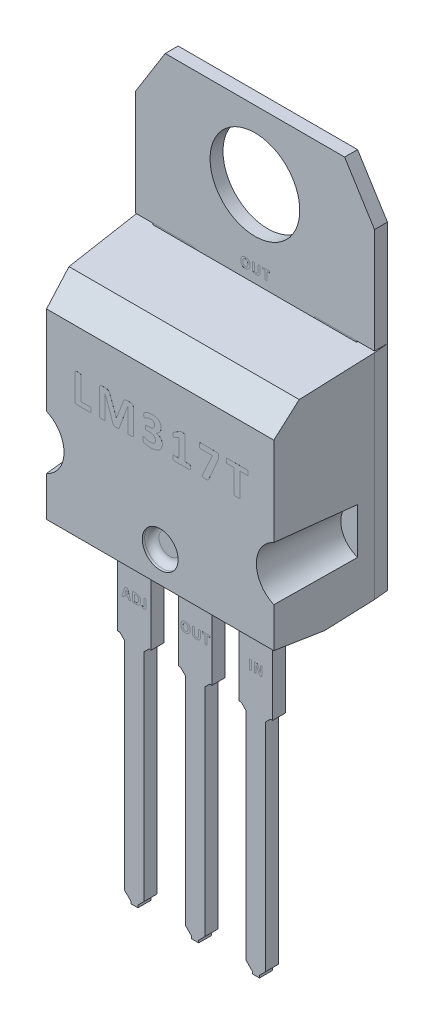
SolidWorks part; units mm, degrees
material "6061-T6 (SS)"
ref_plane "Front Plane" through (0, 0, 0) normal (0, 0, 1) x (1, 0, 0)
ref_plane "Top Plane" through (0, 0, 0) normal (0, 1, 0) x (1, 0, 0)
ref_plane "Right Plane" through (0, 0, 0) normal (1, 0, 0) x (0, 0, -1)
sketch "Sketch1" plane through (0, 0, 0) normal (1, 0, 0) x (0, 0, -1)
  line L0 (-0.27, 0) -> (0.27, 0) construction
  line L1 (0.27, 0) -> (2.77, 0) construction
  line L2 (2.77, 0) -> (2.77, 0.2628) construction
  line L3 (2.77, 0.2628) -> (0.27, 0)
  line L4 (2.77, 0.2628) -> (2.77, 9.2)
  line L5 (-0.27, 0) -> (-1.73, 0) construction
  line L6 (-1.73, 0) -> (-1.73, 0.2102) construction
  line L7 (0.27, 0) -> (-1.73, 0.2102)
  line L8 (-1.73, 0.2102) -> (-1.73, 7.8321)
  line L9 (2.77, 9.2) -> (-0.73, 8.8321)
  line L10 (-0.73, 8.8321) -> (-1.73, 8.727) construction
  line L11 (-1.73, 8.727) -> (-1.73, 7.8321) construction
  line L12 (-1.73, 7.8321) -> (-0.73, 8.8321)
  line L13 (2.77, 9.2) -> (-1.73, 9.2) construction
  line L14 (-1.73, 9.2) -> (-1.73, 8.727) construction
  line L15 (-0.73, 8.8321) -> (-0.73, 9.2) construction
  dimension "D1" = 0.54
  dimension "D2" = 2.5
  dimension "D3" = 9.2
  dimension "D4" = 6
  dimension "D5" = 4.5
  dimension "D6" = 6
  dimension "D7" = 45
  dimension "D8" = 3.5
extrude "Boss-Extrude1" add sketch "Sketch1" along normal mid plane 10
sketch "Sketch2" plane through (0, 0, 0) normal (0, 1, 0) x (1, 0, 0)
  line L0 (0, 0) -> (0, 2.77) construction
  line L1 (5, 2.77) -> (-5, 2.77) construction
  line L2 (-5, 2.77) -> (5, 2.77) construction
  line L3 (5, 2.77) -> (5, 2.23) construction
  line L4 (-5, 2.77) -> (-5, 2.23) construction
  line L5 (0, 0) -> (0, -1.73) construction
  line L6 (5, -1.73) -> (-5, -1.73) construction
  line L7 (-4.75, -1.73) -> (4.75, -1.73) construction
  line L8 (-4.75, -1.73) -> (-5, 2.23)
  line L9 (4.75, -1.73) -> (5, 2.23)
  line L10 (-4.75, -1.73) -> (-5, -1.73)
  line L11 (-5, -1.73) -> (-5, 2.23)
  line L12 (4.75, -1.73) -> (5, -1.73)
  line L13 (5, -1.73) -> (5, 2.23)
  dimension "D1" = 0.54
  dimension "D2" = 9.5
extrude "Cut-Extrude1" cut sketch "Sketch2" along normal through all
sketch "Sketch3" plane through (0, 0, -2.77) normal (0, 0, -1) x (-1, 0, 0)
  line L0 (0, 0) -> (0, 2.75) construction
  line L1 (-5, 9.2) -> (5, 9.2) construction
  line L2 (-4.25, 9.2) -> (4.25, 9.2)
  line L3 (-4.25, 9.2) -> (-4.25, 2.75)
  line L4 (-4.25, 2.75) -> (4.25, 2.75)
  line L5 (4.25, 9.2) -> (4.25, 2.75)
  dimension "D1" = 8.5
  dimension "D2" = 2.75
extrude "Cut-Extrude2" cut sketch "Sketch3" against normal blind 0.54
sketch "Sketch4" plane through (0, 0, -2.23) normal (0, 0, -1) x (-1, 0, 0)
  line L0 (-4.25, 2.75) -> (4.25, 2.75)
  line L1 (4.25, 2.75) -> (4.25, 9.2)
  line L2 (4.25, 9.2) -> (5, 9.2)
  line L3 (5, 9.2) -> (5, 13.6)
  line L4 (-4.25, 2.75) -> (-4.25, 9.2)
  line L5 (-4.25, 9.2) -> (-5, 9.2)
  line L6 (-5, 9.2) -> (-5, 13.6)
  line L7 (0, 0) -> (0, 2.75) construction
  line L8 (0, 2.75) -> (0, 12.73) construction
  line L9 (0, 12.73) -> (0, 15.6) construction
  line L10 (-3.75, 15.6) -> (3.75, 15.6)
  line L11 (-3.75, 15.6) -> (-5, 13.6)
  line L12 (3.75, 15.6) -> (5, 13.6)
  line L13 (-3.75, 15.6) -> (-5, 15.6) construction
  line L14 (-5, 15.6) -> (-5, 13.6) construction
  line L15 (3.75, 15.6) -> (5, 15.6) construction
  line L16 (5, 15.6) -> (5, 13.6) construction
  circle A0 centre (0, 12.73) radius 1.875
  point P21 (0, 14.605)
  dimension "D5" = 3.75
  dimension "D1" = 7.5
  dimension "D2" = 15.6
  dimension "D3" = 2
  dimension "D4" = 2.87
  dimension "D6" = 0.995
extrude "Boss-Extrude2" add sketch "Sketch4" along normal blind 0.54 separate body
sketch "Sketch5" plane through (0, 0, 0) normal (0, 0, 1) x (1, 0, 0)
  line L0 (0, 2.75) -> (0, -13.4) construction
  line L1 (4.25, 2.75) -> (-4.25, 2.75) construction
  line L2 (0, 2.75) -> (0, 5) construction
  line L3 (-0.15, -13.4) -> (0.15, -13.4)
  line L4 (0.15, -13.4) -> (0.15, -13.3)
  line L5 (-0.15, -13.4) -> (-0.15, -13.3)
  line L6 (0.15, -13.4) -> (0.41, -13.4) construction
  line L7 (-0.15, -13.4) -> (-0.41, -13.4) construction
  line L8 (0.41, -13.4) -> (0.41, -13.04) construction
  line L9 (0.41, -13.04) -> (0.15, -13.3)
  line L10 (-0.41, -13.4) -> (-0.41, -13.04) construction
  line L11 (-0.41, -13.04) -> (-0.15, -13.3)
  line L12 (0, 5) -> (0, 12.73) construction
  line L13 (0, 12.73) -> (0, 15.6) construction
  line L14 (-3.75, 15.6) -> (3.75, 15.6) construction
  line L15 (0.41, -13.04) -> (0.41, -3.8)
  line L16 (0.41, -3.8) -> (0.7, -3.8)
  line L17 (0.7, -3.8) -> (0.7, -1.1)
  line L18 (0.7, -1.1) -> (0.7, -1) construction
  line L19 (0.7, -1) -> (0.6, -1) construction
  line L20 (0.6, -1) -> (0.7, -1.1)
  line L21 (0.6, 5) -> (-0.6, 5)
  line L22 (0.6, 5) -> (0.6, -1)
  line L23 (-0.6, 5) -> (-0.6, -1)
  line L24 (-0.41, -13.04) -> (-0.41, -3.8)
  line L25 (0.41, -3.8) -> (0, -3.8) construction
  line L26 (0, -3.8) -> (-0.41, -3.8) construction
  line L27 (-0.41, -3.8) -> (-0.7, -3.8)
  line L28 (-0.7, -3.8) -> (-0.7, -1.1)
  line L29 (-0.6, -1) -> (-0.7, -1) construction
  line L30 (-0.7, -1) -> (-0.7, -1.1) construction
  line L31 (-0.6, -1) -> (-0.7, -1.1)
  line L32 (0.6, -1) -> (0, -1) construction
  line L33 (0, -1) -> (-0.6, -1) construction
  dimension "D1" = 5
  dimension "D2" = 0.3
  dimension "D3" = 0.82
  dimension "D4" = 45
  dimension "D5" = 0.1
  dimension "D6" = 29
  dimension "D7" = 1.2
  dimension "D8" = 45
  dimension "D9" = 1.4
  dimension "D10" = 3.8
  dimension "D11" = 1
  dimension "D12" = 13.4
  dimension "D13" = 16.53
  dimension "D14" = 2.87
extrude "Boss-Extrude3" add sketch "Sketch5" along normal mid plane 0.54
pattern_linear "LPattern2" count 2 spacing 2.54 along (1, 0, 0) count 2 spacing 2.54 along (-1, 0, 0) of "Boss-Extrude3"
sketch "Sketch6" plane through (0, 0, 1.73) normal (0, 0, 1) x (1, 0, 0)
  line L0 (0, 0) -> (0, 1.5) construction
  line L1 (0, 1.5) -> (0, 3) construction
  line L2 (0, 3) -> (0, 12.73) construction
  line L3 (-5.25, 3) -> (5.25, 3) construction
  circle A0 centre (0, 1.5) radius 0.75
  circle A1 centre (5.25, 3) radius 1 construction
  circle A2 centre (-5.25, 3) radius 1 construction
  dimension "D1" = 1.5
  dimension "D2" = 1.5
  dimension "D4" = 10.5
  dimension "D5" = 2
  dimension "D3" = 3
extrude "Cut-Extrude3" cut sketch "Sketch6" against normal blind 0.4
fillet "Fillet1" radius 0.3 1 edges at (0.75, 1.5, 1.33)
ref_plane "Plane1" through (0, 0, -1.57) normal (0, 0, -1) x (-1, 0, 0)
sketch "Sketch7" plane through (0, 0, -1.57) normal (0, 0, -1) x (-1, 0, 0)
  circle A0 centre (-5.25, 3) radius 1 construction
  circle A1 centre (5.25, 3) radius 1 construction
  circle A2 centre (-5.25, 3) radius 1
  circle A3 centre (5.25, 3) radius 1
extrude "Cut-Extrude9" cut sketch "Sketch7" against normal up to surface (3.3 mm away) draft 4
sketch "Sketch8" plane through (0, -13.4, 0) normal (0, -1, 0) x (1, 0, 0)
  line L0 (-2.54, 0) -> (2.54, 0) construction
  circle A0 centre (0, 0) radius 0.1
  circle A1 centre (-2.54, 0) radius 0.1
  circle A2 centre (2.54, 0) radius 0.1
  dimension "D1" = 0.2
  dimension "D2" = 5.08
extrude "Cut-Extrude10" cut sketch "Sketch8" against normal blind 0.01
sketch "Sketch10" plane through (0, 0, -2.77) normal (0, 0, -1) x (-1, 0, 0)
  line L0 (-4.25, 3.75) -> (-3.5, 3.75)
  line L1 (-4.25, 9.2) -> (-4.25, 2.75) construction
  line L2 (-3.5, 3.75) -> (-3.5, 8.2)
  line L3 (-3.5, 8.2) -> (-2.5, 8.2)
  line L4 (-2.5, 8.2) -> (-2.5, 9.2)
  line L5 (-2.5, 9.2) -> (-4.25, 9.2)
  line L6 (-4.25, 9.2) -> (-4.25, 3.75)
  line L7 (4.25, 9.2) -> (2.5, 9.2)
  line L8 (2.5, 9.2) -> (2.5, 8.2)
  line L9 (2.5, 8.2) -> (3.5, 8.2)
  line L10 (3.5, 8.2) -> (3.5, 3.75)
  line L11 (3.5, 3.75) -> (4.25, 3.75)
  line L12 (4.25, 2.75) -> (4.25, 9.2) construction
  line L13 (4.25, 3.75) -> (4.25, 9.2)
  line L14 (-4.25, 2.75) -> (4.25, 2.75) construction
  dimension "D1" = 7
  dimension "D2" = 5
  dimension "D3" = 1
  dimension "D4" = 1
extrude "Cut-Extrude11" cut sketch "Sketch10" against normal up to surface (0.54 mm away) up to face at (0, 10.07, -2.23)
sketch "Sketch11" plane through (0, 0, -2.23) normal (0, 0, -1) x (-1, 0, 0)
  line L6 (-4.25, 3.75) -> (-3.5, 3.75)
  line L7 (-3.5, 3.75) -> (-3.5, 8.2)
  line L8 (-3.5, 8.2) -> (-2.5, 8.2)
  line L9 (-2.5, 8.2) -> (-2.5, 9.2)
  line L10 (-2.5, 9.2) -> (-4.25, 9.2)
  line L11 (-4.25, 9.2) -> (-4.25, 3.75)
  line L12 (-4.25, 3.75) -> (-3.5, 3.75)
  line L13 (-3.5, 3.75) -> (-3.5, 8.2)
  line L14 (-3.5, 8.2) -> (-2.5, 8.2)
  line L15 (-2.5, 8.2) -> (-2.5, 9.2)
  line L16 (-2.5, 9.2) -> (-4.25, 9.2)
  line L17 (-4.25, 9.2) -> (-4.25, 3.75)
  line L18 (3.5, 3.75) -> (4.25, 3.75)
  line L19 (3.5, 8.2) -> (3.5, 3.75)
  line L20 (2.5, 8.2) -> (3.5, 8.2)
  line L21 (2.5, 9.2) -> (2.5, 8.2)
  line L22 (4.25, 9.2) -> (2.5, 9.2)
  line L23 (4.25, 3.75) -> (4.25, 9.2)
  line L24 (3.5, 3.75) -> (4.25, 3.75)
  line L25 (3.5, 8.2) -> (3.5, 3.75)
  line L26 (2.5, 8.2) -> (3.5, 8.2)
  line L27 (2.5, 9.2) -> (2.5, 8.2)
  line L28 (4.25, 9.2) -> (2.5, 9.2)
  line L29 (4.25, 3.75) -> (4.25, 9.2)
  dimension "D1" = 0
  dimension "D2" = 0
extrude "Boss-Extrude4" add sketch "Sketch11" along normal up to surface (0.54 mm away) up to face at (0, 5.3532, -2.77)
chamfer "Chamfer1" distance 0.2 angle 45 6 edges at (2.95, -3.8, 0) (2.13, -3.8, 0) (-2.95, -3.8, 0) (-2.13, -3.8, 0) (-0.41, -3.8, 0) (0.41, -3.8, 0)
sketch "Sketch12" plane through (0, 0, 1.73) normal (0, 0, 1) x (1, 0, 0)
  line L0 (0, 0) -> (0, 5) construction
  line L1 (-4.75, 5) -> (4.75, 5) construction
  line L2 (-4.75, 7.8321) -> (-4.75, 4.1246) construction
  text T0 "LM317T" font "Calibri" height 1.2
  point P5 (-4.75, 4.6237)
  dimension "D1" = 5
extrude "Boss-Extrude5" add sketch "Sketch12" along normal blind 0.001
sketch "Sketch13" plane through (0, 0, -2.77) normal (0, 0, -1) x (-1, 0, 0)
  line L0 (0, 0) -> (0, 3.75) construction
  line L1 (-0.6, 0) -> (0.6, 0) construction
  line L2 (0, 3.75) -> (0, 5.2) construction
  line L3 (0, 5.2) -> (0, 7) construction
  line L4 (-3.5, 7) -> (3.5, 7) construction
  line L5 (-3.5, 8.2) -> (-3.5, 3.75) construction
  line L6 (3.5, 5.2) -> (-3.5, 5.2) construction
  line L7 (3.5, 3.75) -> (-3.5, 3.75) construction
  line L8 (0, 7) -> (0, 9.5) construction
  line L9 (-5, 9.5) -> (5, 9.5) construction
  line L10 (-5, 13.6) -> (-5, 9.2) construction
  line L11 (5, 9.2) -> (5, 13.6) construction
  text T0 "Adjustable" font "Century Gothic" height 0.7
  text T1 "LM317T" font "Century Gothic" height 1
  text T2 "Voltage" font "Century Gothic" height 0.8
  text T3 "Regulator" font "Century Gothic" height 0.8
  point P19 (0, 9.3592)
  point P25 (0, 7.0686)
  point P27 (0, 5.7752)
  point P28 (0, 5.1316)
  point P29 (0, 7)
  dimension "D1" = 9.5
  dimension "D2" = 7
  dimension "D3" = 5.2
extrude "Cut-Extrude12" cut sketch "Sketch13" against normal blind 0.001
sketch "Sketch14" plane through (0, 0, 0.27) normal (0, 0, 1) x (1, 0, 0)
  line L0 (-0.7, -2.45) -> (0.7, -2.45) construction
  line L1 (-0.7, -1.1) -> (-0.7, -3.8) construction
  line L2 (0.7, -3.8) -> (0.7, -1.1) construction
  line L3 (0.7, -2.45) -> (1.84, -2.45) construction
  line L4 (1.84, -1.1) -> (1.84, -3.8) construction
  line L5 (1.84, -2.45) -> (3.24, -2.45) construction
  line L6 (3.24, -3.8) -> (3.24, -1.1) construction
  line L7 (-0.7, -2.45) -> (-1.84, -2.45) construction
  line L8 (-1.84, -3.8) -> (-1.84, -1.1) construction
  line L9 (-1.84, -2.45) -> (-3.24, -2.45) construction
  line L10 (-3.24, -1.1) -> (-3.24, -3.8) construction
  text T0 "ADJ" font "Calibri" height 0.4
  text T1 "OUT" font "Calibri" height 0.4
  text T2 "IN" font "Calibri" height 0.4
extrude "Boss-Extrude6" add sketch "Sketch14" along normal blind 0.001
sketch "Sketch15" plane through (0, 0, -0.27) normal (0, 0, -1) x (-1, 0, 0)
  line L0 (-0.7, -2.45) -> (0.7, -2.45) construction
  line L1 (-0.7, -3.8) -> (-0.7, -1.1) construction
  line L2 (0.7, -1.1) -> (0.7, -3.8) construction
  line L3 (0.7, -2.45) -> (1.84, -2.45) construction
  line L4 (1.84, -3.8) -> (1.84, -1.1) construction
  line L5 (1.84, -2.45) -> (3.24, -2.45) construction
  line L6 (3.24, -1.1) -> (3.24, -3.8) construction
  line L7 (-0.7, -2.45) -> (-1.84, -2.45) construction
  line L8 (-1.84, -1.1) -> (-1.84, -3.8) construction
  line L9 (-1.84, -2.45) -> (-3.24, -2.45) construction
  line L10 (-3.24, -3.8) -> (-3.24, -1.1) construction
  text T0 "IN" font "Calibri" height 0.4
  text T1 "OUT" font "Calibri" height 0.4
  text T2 "ADJ" font "Calibri" height 0.4
extrude "Boss-Extrude7" add sketch "Sketch15" along normal blind 0.001
sketch "Sketch16" plane through (0, 0, -2.23) normal (0, 0, 1) x (1, 0, 0)
  line L0 (0, 0) -> (0, 9.5) construction
  line L1 (-1.5, 9.5) -> (1.5, 9.5) construction
  text T0 "OUT" font "Calibri" height 0.4
  dimension "D1" = 9.5
  dimension "D2" = 3
extrude "Cut-Extrude13" cut sketch "Sketch16" against normal blind 0.001
